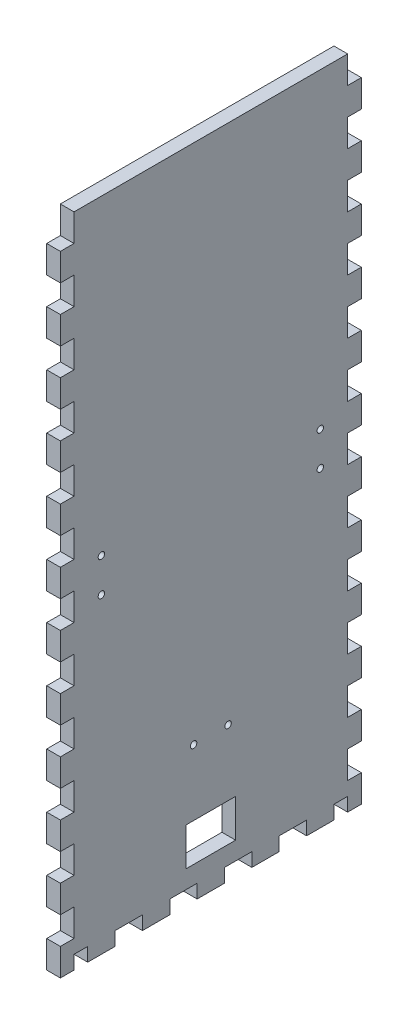
SolidWorks part; units mm, degrees
material "Acrylic (Medium-high impact)"
ref_plane "Front Plane" through (0, 0, 0) normal (0, 0, 1) x (1, 0, 0)
ref_plane "Top Plane" through (0, 0, 0) normal (0, 1, 0) x (1, 0, 0)
ref_plane "Right Plane" through (0, 0, 0) normal (1, 0, 0) x (0, 0, -1)
sketch "Sketch1" plane through (0, 0, 0) normal (0, 1, 0) x (1, 0, 0)
  line L1 (-136.525, 69.85) -> (136.525, 69.85)
  line L2 (-136.525, 69.85) -> (-136.525, -69.85)
  line L3 (-136.525, -69.85) -> (136.525, -69.85)
  line L4 (136.525, 69.85) -> (136.525, -69.85)
  point P4 (-136.525, 0)
  point P6 (0, 69.85)
  dimension "D1" = 139.7
  dimension "D2" = 273.05
extrude "Boss-Extrude1" add sketch "Sketch1" along normal blind 6.35
sketch "Sketch2" plane through (0, 6.35, 0) normal (0, 1, 0) x (1, 0, 0)
  line L0 (136.525, -69.85) -> (136.525, 69.85) construction
  line L1 (-136.525, 69.85) -> (136.525, 69.85)
  line L2 (-136.525, 69.85) -> (-136.525, -69.85)
  line L3 (-136.525, -69.85) -> (136.525, -69.85)
  line L4 (136.525, 69.85) -> (136.525, -69.85)
  line L5 (-136.525, -69.85) -> (136.525, -69.85) construction
  line L7 (-130.175, 63.5) -> (130.175, 63.5)
  line L8 (-130.175, 63.5) -> (-130.175, -63.5)
  line L9 (-130.175, -63.5) -> (130.175, -63.5)
  line L10 (130.175, 63.5) -> (130.175, -63.5)
  point P7 (-130.175, 0)
  point P14 (-136.525, 0)
  point P15 (0, -63.5)
  point P16 (0, -69.85)
  point P17 (130.175, 0)
  point P18 (136.525, 0)
  dimension "D1" = 6.35
  dimension "D2" = 6.35
extrude "Boss-Extrude2" add sketch "Sketch2" along normal blind 298.45
sketch "Sketch3" plane through (0, 0, 69.85) normal (0, 0, 1) x (1, 0, 0)
  line L0 (-25.273, 304.8) -> (-25.273, 0) construction
  line L2 (-130.175, 6.35) -> (130.175, 6.35) construction
  line L4 (-28.575, 283.21) -> (-28.575, 6.35)
  line L5 (-28.575, 6.35) -> (-21.971, 6.35)
  line L6 (-21.971, 292.354) -> (-21.971, 6.35)
  line L7 (-21.971, 292.354) -> (-41.529, 292.354)
  line L9 (-31.115, 285.75) -> (-41.529, 285.75)
  line L10 (-41.529, 292.354) -> (-41.529, 285.75)
  line L11 (-21.971, 101.6) -> (-9.271, 101.6) construction
  line L12 (-136.525, 0) -> (136.525, 0) construction
  line L13 (-12.446, 88.9) -> (-12.446, 101.6) construction
  line L14 (-15.621, 88.9) -> (-9.271, 88.9)
  line L15 (-15.621, 88.9) -> (-15.621, 71.9667)
  line L16 (-15.621, 71.9667) -> (-9.271, 71.9667)
  line L17 (-9.271, 88.9) -> (-9.271, 71.9667)
  line L18 (-15.621, 42.3333) -> (-9.271, 42.3333)
  line L19 (-15.621, 42.3333) -> (-15.621, 59.2667)
  line L20 (-15.621, 59.2667) -> (-9.271, 59.2667)
  line L21 (-9.271, 42.3333) -> (-9.271, 59.2667)
  line L26 (-15.621, 29.6333) -> (-9.271, 29.6333)
  line L27 (-15.621, 29.6333) -> (-15.621, 12.7)
  line L28 (-15.621, 12.7) -> (-9.271, 12.7)
  line L29 (-9.271, 29.6333) -> (-9.271, 12.7)
  line L30 (-12.446, 59.2667) -> (-12.446, 71.9667) construction
  line L31 (-12.446, 29.6333) -> (-12.446, 42.3333) construction
  line L32 (-12.446, 12.7) -> (-12.446, 0) construction
  line L33 (-136.525, 304.8) -> (136.525, 304.8) construction
  line L34 (-130.175, 304.8) -> (-130.175, 6.35) construction
  arc A0 (-28.575, 283.21) -> (-31.115, 285.75) centre (-31.115, 283.21) ccw
  point P5 (-25.273, 6.35)
  dimension "D5" = 2.54
  dimension "D1" = 6.604
  dimension "D2" = 12.954
  dimension "D3" = 6.604
  dimension "D4" = 286.004
  dimension "D6" = 101.6
  dimension "D7" = 12.7
  dimension "D8" = 12.7
  dimension "D9" = 6.35
  dimension "D10" = 101.6
extrude "Door Slot" cut sketch "Sketch3" against normal blind 12.7
sketch "Sketch4" plane through (0, 0, -63.5) normal (0, 0, 1) x (1, 0, 0)
  line L0 (-136.525, 304.8) -> (136.525, 304.8) construction
  line L1 (-47.879, 304.8) -> (-41.529, 304.8)
  line L2 (-47.879, 304.8) -> (-47.879, 6.35)
  line L3 (-47.879, 6.35) -> (-41.529, 6.35)
  line L4 (-41.529, 304.8) -> (-41.529, 6.35)
  line L5 (-18.796, 263.525) -> (-18.796, 247.65) construction
  line L6 (-41.529, 292.354) -> (-41.529, 285.75) construction
  line L7 (-21.971, 304.8) -> (-15.621, 304.8)
  line L8 (-21.971, 304.8) -> (-21.971, 6.35)
  line L9 (-21.971, 6.35) -> (-15.621, 6.35)
  line L10 (-15.621, 304.8) -> (-15.621, 6.35)
  line L11 (130.175, 6.35) -> (-130.175, 6.35) construction
  line L12 (-21.971, 6.35) -> (-21.971, 292.354) construction
  line L13 (-41.529, 304.8) -> (-47.879, 304.8)
  line L14 (-41.529, 304.8) -> (-41.529, 292.1)
  line L15 (-41.529, 292.1) -> (-47.879, 292.1)
  line L16 (-47.879, 304.8) -> (-47.879, 292.1)
  line L17 (-41.529, 276.225) -> (-47.879, 276.225)
  line L18 (-41.529, 276.225) -> (-41.529, 263.525)
  line L19 (-41.529, 263.525) -> (-47.879, 263.525)
  line L20 (-47.879, 276.225) -> (-47.879, 263.525)
  line L21 (-47.879, 6.35) -> (-41.529, 6.35)
  line L22 (-47.879, 6.35) -> (-47.879, 19.05)
  line L23 (-47.879, 19.05) -> (-41.529, 19.05)
  line L24 (-41.529, 6.35) -> (-41.529, 19.05)
  line L25 (-47.879, 34.925) -> (-41.529, 34.925)
  line L26 (-47.879, 34.925) -> (-47.879, 47.625)
  line L27 (-47.879, 47.625) -> (-41.529, 47.625)
  line L28 (-41.529, 34.925) -> (-41.529, 47.625)
  line L29 (-47.879, 92.075) -> (-41.529, 92.075)
  line L30 (-47.879, 92.075) -> (-47.879, 104.775)
  line L31 (-47.879, 104.775) -> (-41.529, 104.775)
  line L32 (-41.529, 92.075) -> (-41.529, 104.775)
  line L33 (-47.879, 149.225) -> (-41.529, 149.225)
  line L34 (-47.879, 149.225) -> (-47.879, 161.925)
  line L35 (-47.879, 161.925) -> (-41.529, 161.925)
  line L36 (-41.529, 149.225) -> (-41.529, 161.925)
  line L37 (-47.879, 177.8) -> (-41.529, 177.8)
  line L38 (-47.879, 177.8) -> (-47.879, 190.5)
  line L39 (-47.879, 190.5) -> (-41.529, 190.5)
  line L40 (-41.529, 177.8) -> (-41.529, 190.5)
  line L41 (-47.879, 206.375) -> (-41.529, 206.375)
  line L42 (-47.879, 206.375) -> (-47.879, 219.075)
  line L43 (-47.879, 219.075) -> (-41.529, 219.075)
  line L44 (-41.529, 206.375) -> (-41.529, 219.075)
  line L45 (-47.879, 234.95) -> (-41.529, 234.95)
  line L46 (-47.879, 234.95) -> (-47.879, 247.65)
  line L47 (-47.879, 247.65) -> (-41.529, 247.65)
  line L48 (-41.529, 234.95) -> (-41.529, 247.65)
  line L49 (-41.529, 133.35) -> (-47.879, 133.35)
  line L50 (-41.529, 133.35) -> (-41.529, 120.65)
  line L51 (-41.529, 120.65) -> (-47.879, 120.65)
  line L52 (-47.879, 133.35) -> (-47.879, 120.65)
  line L53 (-41.529, 76.2) -> (-47.879, 76.2)
  line L54 (-41.529, 76.2) -> (-41.529, 63.5)
  line L55 (-41.529, 63.5) -> (-47.879, 63.5)
  line L56 (-47.879, 76.2) -> (-47.879, 63.5)
  line L57 (-44.704, 304.8) -> (-44.704, 292.1) construction
  line L58 (-44.704, 292.1) -> (-44.704, 276.225) construction
  line L59 (-44.704, 276.225) -> (-44.704, 263.525) construction
  line L60 (-44.704, 247.65) -> (-44.704, 234.95) construction
  line L61 (-44.704, 234.95) -> (-44.704, 219.075) construction
  line L62 (-44.704, 219.075) -> (-44.704, 206.375) construction
  line L63 (-44.704, 206.375) -> (-44.704, 190.5) construction
  line L64 (-44.704, 190.5) -> (-44.704, 177.8) construction
  line L65 (-44.704, 177.8) -> (-44.704, 161.925) construction
  line L66 (-44.704, 161.925) -> (-44.704, 149.225) construction
  line L67 (-44.704, 133.35) -> (-44.704, 120.65) construction
  line L68 (-44.704, 120.65) -> (-44.704, 104.775) construction
  line L69 (-44.704, 104.775) -> (-44.704, 92.075) construction
  line L70 (-44.704, 92.075) -> (-44.704, 76.2) construction
  line L71 (-44.704, 76.2) -> (-44.704, 63.5) construction
  line L72 (-44.704, 63.5) -> (-44.704, 47.625) construction
  line L73 (-44.704, 47.625) -> (-44.704, 34.925) construction
  line L74 (-44.704, 34.925) -> (-44.704, 19.05) construction
  line L75 (-44.704, 19.05) -> (-44.704, 6.35) construction
  line L76 (-44.704, 149.225) -> (-44.704, 133.35) construction
  line L77 (-44.704, 263.525) -> (-44.704, 247.65) construction
  line L78 (-31.75, 304.8) -> (-31.75, 0) construction
  line L79 (136.525, 304.8) -> (-136.525, 304.8) construction
  line L80 (136.525, 0) -> (-136.525, 0) construction
  line L81 (-31.75, 8.3493) -> (-21.971, 8.3493) construction
  line L82 (-31.75, 8.3493) -> (-41.529, 8.3493) construction
  line L83 (-18.796, 149.225) -> (-18.796, 133.35) construction
  line L84 (-18.796, 19.05) -> (-18.796, 6.35) construction
  line L85 (-18.796, 34.925) -> (-18.796, 19.05) construction
  line L86 (-18.796, 47.625) -> (-18.796, 34.925) construction
  line L87 (-18.796, 63.5) -> (-18.796, 47.625) construction
  line L88 (-18.796, 76.2) -> (-18.796, 63.5) construction
  line L89 (-18.796, 92.075) -> (-18.796, 76.2) construction
  line L90 (-18.796, 104.775) -> (-18.796, 92.075) construction
  line L91 (-18.796, 120.65) -> (-18.796, 104.775) construction
  line L92 (-18.796, 133.35) -> (-18.796, 120.65) construction
  line L93 (-18.796, 161.925) -> (-18.796, 149.225) construction
  line L94 (-18.796, 177.8) -> (-18.796, 161.925) construction
  line L95 (-18.796, 190.5) -> (-18.796, 177.8) construction
  line L96 (-18.796, 206.375) -> (-18.796, 190.5) construction
  line L97 (-18.796, 219.075) -> (-18.796, 206.375) construction
  line L98 (-18.796, 234.95) -> (-18.796, 219.075) construction
  line L99 (-18.796, 247.65) -> (-18.796, 234.95) construction
  line L100 (-18.796, 276.225) -> (-18.796, 263.525) construction
  line L101 (-18.796, 292.1) -> (-18.796, 276.225) construction
  line L102 (-18.796, 304.8) -> (-18.796, 292.1) construction
  line L103 (-15.621, 76.2) -> (-15.621, 63.5)
  line L104 (-21.971, 63.5) -> (-15.621, 63.5)
  line L105 (-21.971, 76.2) -> (-21.971, 63.5)
  line L106 (-21.971, 76.2) -> (-15.621, 76.2)
  line L107 (-15.621, 133.35) -> (-15.621, 120.65)
  line L108 (-21.971, 120.65) -> (-15.621, 120.65)
  line L109 (-21.971, 133.35) -> (-21.971, 120.65)
  line L110 (-21.971, 133.35) -> (-15.621, 133.35)
  line L111 (-21.971, 234.95) -> (-21.971, 247.65)
  line L112 (-15.621, 247.65) -> (-21.971, 247.65)
  line L113 (-15.621, 234.95) -> (-15.621, 247.65)
  line L114 (-15.621, 234.95) -> (-21.971, 234.95)
  line L115 (-21.971, 206.375) -> (-21.971, 219.075)
  line L116 (-15.621, 219.075) -> (-21.971, 219.075)
  line L117 (-15.621, 206.375) -> (-15.621, 219.075)
  line L118 (-15.621, 206.375) -> (-21.971, 206.375)
  line L119 (-21.971, 177.8) -> (-21.971, 190.5)
  line L120 (-15.621, 190.5) -> (-21.971, 190.5)
  line L121 (-15.621, 177.8) -> (-15.621, 190.5)
  line L122 (-15.621, 177.8) -> (-21.971, 177.8)
  line L123 (-21.971, 149.225) -> (-21.971, 161.925)
  line L124 (-15.621, 161.925) -> (-21.971, 161.925)
  line L125 (-15.621, 149.225) -> (-15.621, 161.925)
  line L126 (-15.621, 149.225) -> (-21.971, 149.225)
  line L127 (-21.971, 92.075) -> (-21.971, 104.775)
  line L128 (-15.621, 104.775) -> (-21.971, 104.775)
  line L129 (-15.621, 92.075) -> (-15.621, 104.775)
  line L130 (-15.621, 92.075) -> (-21.971, 92.075)
  line L131 (-21.971, 34.925) -> (-21.971, 47.625)
  line L132 (-15.621, 47.625) -> (-21.971, 47.625)
  line L133 (-15.621, 34.925) -> (-15.621, 47.625)
  line L134 (-15.621, 34.925) -> (-21.971, 34.925)
  line L135 (-21.971, 6.35) -> (-21.971, 19.05)
  line L136 (-15.621, 19.05) -> (-21.971, 19.05)
  line L137 (-15.621, 6.35) -> (-15.621, 19.05)
  line L138 (-15.621, 6.35) -> (-21.971, 6.35)
  line L139 (-15.621, 276.225) -> (-15.621, 263.525)
  line L140 (-21.971, 263.525) -> (-15.621, 263.525)
  line L141 (-21.971, 276.225) -> (-21.971, 263.525)
  line L142 (-21.971, 276.225) -> (-15.621, 276.225)
  line L143 (-15.621, 304.8) -> (-15.621, 292.1)
  line L144 (-21.971, 292.1) -> (-15.621, 292.1)
  line L145 (-21.971, 304.8) -> (-21.971, 292.1)
  line L146 (-21.971, 304.8) -> (-15.621, 304.8)
  line L147 (-21.971, 304.8) -> (-21.971, 6.35)
  line L148 (-15.621, 6.35) -> (-21.971, 6.35)
  line L149 (-15.621, 304.8) -> (-15.621, 6.35)
  line L150 (-15.621, 304.8) -> (-21.971, 304.8)
  point P14 (-41.529, 289.052)
  dimension "D1" = 6.35
  dimension "D2" = 12.7
extrude "Door Guide Holes" cut sketch "Sketch4" against normal up to next contours L17 L4 L15 L2 | L2 L47 L4 L19 | L45 L2 L43 L4 | L41 L2 L39 L4 | L37 L2 L35 L4 | L49 L4 L33 L2 | L4 L51 L2 L31 | L53 L4 L29 L2 | L4 L55 L2 L27 | L25 L2 L23 L4 region at (-44.704, 284.1625, -63.5) region at (-44.704, 255.5875, -63.5) region at (-44.704, 227.0125, -63.5) region at (-44.704, 198.4375, -63.5) region at (-44.704, 169.8625, -63.5) region at (-44.704, 141.2875, -63.5) region at (-44.704, 112.7125, -63.5) region at (-44.704, 84.1375, -63.5) region at (-44.704, 55.5625, -63.5) region at (-44.704, 26.9875, -63.5)
ref_plane "Plane1" through (-31.75, 0, 0) normal (-1, 0, 0) x (0, 0, 1)
mirror "Mirror1" about plane through (-31.75, 0, 0) normal (-1, 0, 0) of "Door Guide Holes"
sketch "Lever Holes" plane through (0, 0, 69.85) normal (0, 0, 1) x (1, 0, 0)
  line L0 (49.276, 31.75) -> (58.928, 31.75)
  line L1 (49.276, 31.75) -> (49.276, 25.4)
  line L2 (49.276, 25.4) -> (58.928, 25.4)
  line L3 (58.928, 31.75) -> (58.928, 25.4)
  line L4 (36.1315, 19.05) -> (42.4815, 19.05)
  line L5 (36.1315, 19.05) -> (36.1315, 12.7)
  line L6 (36.1315, 12.7) -> (42.4815, 12.7)
  line L7 (42.4815, 19.05) -> (42.4815, 12.7)
  line L8 (65.7225, 19.05) -> (72.0725, 19.05)
  line L9 (65.7225, 19.05) -> (65.7225, 12.7)
  line L10 (65.7225, 12.7) -> (72.0725, 12.7)
  line L11 (72.0725, 19.05) -> (72.0725, 12.7)
  line L12 (42.4815, 15.875) -> (65.7225, 15.875) construction
  line L13 (-136.525, 0) -> (136.525, 0) construction
  line L14 (-21.971, 6.35) -> (130.175, 6.35) construction
  line L15 (130.175, 6.35) -> (-130.175, 6.35) construction
  point P12 (54.102, 15.875)
  point P13 (54.102, 25.4)
  point P24 (54.102, 6.35)
  dimension "D1" = 9.652
  dimension "D2" = 6.35
  dimension "D3" = 6.35
  dimension "D4" = 6.35
  dimension "D5" = 23.241
  dimension "D6" = 25.4
  dimension "D7" = 12.7
extrude "Cut-Extrude1" cut sketch "Lever Holes" against normal through all
sketch "Sketch8" plane through (-136.525, 0, 0) normal (-1, 0, 0) x (0, 0, 1)
  line L0 (-69.85, 0) -> (69.85, 0) construction
  circle A0 centre (0, 19.05) radius 3.175
  point P6 (0, 0)
  dimension "D1" = 6.35
  dimension "D2" = 19.05
extrude "Cut-Extrude3" cut sketch "Sketch8" against normal up to next
sketch "Bottom" plane through (0, 0, 0) normal (0, -1, 0) x (1, 0, 0)
  line L0 (-130.175, 63.5) -> (130.175, 63.5) construction
  line L1 (-136.525, 69.85) -> (-122.1539, 69.85)
  line L2 (-136.525, 69.85) -> (-136.525, 63.5)
  line L3 (-136.525, 63.5) -> (-122.1539, 63.5)
  line L4 (-122.1539, 69.85) -> (-122.1539, 63.5)
  line L5 (-122.1539, 69.85) -> (-107.7829, 69.85)
  line L6 (-122.1539, 69.85) -> (-122.1539, 63.5)
  line L7 (-122.1539, 63.5) -> (-107.7829, 63.5)
  line L8 (-107.7829, 69.85) -> (-107.7829, 63.5)
  line L9 (-107.7829, 69.85) -> (-93.4118, 69.85)
  line L10 (-107.7829, 69.85) -> (-107.7829, 63.5)
  line L11 (-107.7829, 63.5) -> (-93.4118, 63.5)
  line L12 (-93.4118, 69.85) -> (-93.4118, 63.5)
  line L13 (-93.4118, 69.85) -> (-79.0408, 69.85)
  line L14 (-93.4118, 69.85) -> (-93.4118, 63.5)
  line L15 (-93.4118, 63.5) -> (-79.0408, 63.5)
  line L16 (-79.0408, 69.85) -> (-79.0408, 63.5)
  line L17 (-136.525, 69.85) -> (136.525, 69.85) construction
  line L18 (-41.529, 63.5) -> (-21.971, 63.5) construction
  line L19 (-79.0408, 69.85) -> (-64.6697, 69.85)
  line L20 (-79.0408, 69.85) -> (-79.0408, 63.5)
  line L21 (-79.0408, 63.5) -> (-64.6697, 63.5)
  line L22 (-64.6697, 69.85) -> (-64.6697, 63.5)
  line L23 (-64.6697, 69.85) -> (-50.2987, 69.85)
  line L24 (-64.6697, 69.85) -> (-64.6697, 63.5)
  line L25 (-64.6697, 63.5) -> (-50.2987, 63.5)
  line L26 (-50.2987, 69.85) -> (-50.2987, 63.5)
  line L27 (-50.2987, 69.85) -> (-35.9276, 69.85)
  line L28 (-50.2987, 69.85) -> (-50.2987, 63.5)
  line L29 (-50.2987, 63.5) -> (-35.9276, 63.5)
  line L30 (-35.9276, 69.85) -> (-35.9276, 63.5)
  line L31 (-35.9276, 69.85) -> (-21.5566, 69.85)
  line L32 (-35.9276, 69.85) -> (-35.9276, 63.5)
  line L33 (-35.9276, 63.5) -> (-21.5566, 63.5)
  line L34 (-21.5566, 69.85) -> (-21.5566, 63.5)
  line L36 (-21.5566, 69.85) -> (-7.1855, 69.85)
  line L37 (-21.5566, 69.85) -> (-21.5566, 63.5)
  line L38 (-21.5566, 63.5) -> (-7.1855, 63.5)
  line L39 (-7.1855, 69.85) -> (-7.1855, 63.5)
  line L40 (-7.1855, 69.85) -> (7.1855, 69.85)
  line L41 (-7.1855, 69.85) -> (-7.1855, 63.5)
  line L42 (-7.1855, 63.5) -> (7.1855, 63.5)
  line L43 (7.1855, 69.85) -> (7.1855, 63.5)
  line L44 (7.1855, 69.85) -> (21.5566, 69.85)
  line L45 (7.1855, 69.85) -> (7.1855, 63.5)
  line L46 (7.1855, 63.5) -> (21.5566, 63.5)
  line L47 (21.5566, 69.85) -> (21.5566, 63.5)
  line L48 (21.5566, 69.85) -> (35.9276, 69.85)
  line L49 (21.5566, 69.85) -> (21.5566, 63.5)
  line L50 (21.5566, 63.5) -> (35.9276, 63.5)
  line L51 (35.9276, 69.85) -> (35.9276, 63.5)
  line L52 (35.9276, 69.85) -> (50.2987, 69.85)
  line L53 (35.9276, 69.85) -> (35.9276, 63.5)
  line L54 (35.9276, 63.5) -> (50.2987, 63.5)
  line L55 (50.2987, 69.85) -> (50.2987, 63.5)
  line L56 (50.2987, 69.85) -> (64.6697, 69.85)
  line L57 (50.2987, 69.85) -> (50.2987, 63.5)
  line L58 (50.2987, 63.5) -> (64.6697, 63.5)
  line L59 (64.6697, 69.85) -> (64.6697, 63.5)
  line L60 (64.6697, 69.85) -> (79.0408, 69.85)
  line L61 (64.6697, 69.85) -> (64.6697, 63.5)
  line L62 (64.6697, 63.5) -> (79.0408, 63.5)
  line L63 (79.0408, 69.85) -> (79.0408, 63.5)
  line L64 (79.0408, 69.85) -> (93.4118, 69.85)
  line L65 (79.0408, 69.85) -> (79.0408, 63.5)
  line L66 (79.0408, 63.5) -> (93.4118, 63.5)
  line L67 (93.4118, 69.85) -> (93.4118, 63.5)
  line L68 (93.4118, 69.85) -> (107.7829, 69.85)
  line L69 (93.4118, 69.85) -> (93.4118, 63.5)
  line L70 (93.4118, 63.5) -> (107.7829, 63.5)
  line L71 (107.7829, 69.85) -> (107.7829, 63.5)
  line L72 (107.7829, 69.85) -> (122.1539, 69.85)
  line L73 (107.7829, 69.85) -> (107.7829, 63.5)
  line L74 (107.7829, 63.5) -> (122.1539, 63.5)
  line L75 (122.1539, 69.85) -> (122.1539, 63.5)
  line L76 (-130.175, -63.5) -> (-130.175, 63.5) construction
  line L77 (-136.525, 69.85) -> (-130.175, 69.85)
  line L78 (-136.525, 69.85) -> (-136.525, 57.15)
  line L79 (-136.525, 57.15) -> (-130.175, 57.15)
  line L80 (-130.175, 69.85) -> (-130.175, 57.15)
  line L82 (-136.525, 57.15) -> (-130.175, 57.15)
  line L83 (-136.525, 57.15) -> (-136.525, 44.45)
  line L84 (-136.525, 44.45) -> (-130.175, 44.45)
  line L85 (-130.175, 57.15) -> (-130.175, 44.45)
  line L86 (-136.525, 44.45) -> (-130.175, 44.45)
  line L87 (-136.525, 44.45) -> (-136.525, 31.75)
  line L88 (-136.525, 31.75) -> (-130.175, 31.75)
  line L89 (-130.175, 44.45) -> (-130.175, 31.75)
  line L90 (-136.525, 31.75) -> (-130.175, 31.75)
  line L91 (-136.525, 31.75) -> (-136.525, 19.05)
  line L92 (-136.525, 19.05) -> (-130.175, 19.05)
  line L93 (-130.175, 31.75) -> (-130.175, 19.05)
  line L94 (-136.525, 19.05) -> (-130.175, 19.05)
  line L95 (-136.525, 19.05) -> (-136.525, 6.35)
  line L96 (-136.525, 6.35) -> (-130.175, 6.35)
  line L97 (-130.175, 19.05) -> (-130.175, 6.35)
  line L98 (-136.525, 6.35) -> (-130.175, 6.35)
  line L99 (-136.525, 6.35) -> (-136.525, -6.35)
  line L100 (-136.525, -6.35) -> (-130.175, -6.35)
  line L101 (-130.175, 6.35) -> (-130.175, -6.35)
  line L102 (-136.525, -6.35) -> (-130.175, -6.35)
  line L103 (-136.525, -6.35) -> (-136.525, -19.05)
  line L104 (-136.525, -19.05) -> (-130.175, -19.05)
  line L105 (-130.175, -6.35) -> (-130.175, -19.05)
  line L106 (-136.525, -19.05) -> (-130.175, -19.05)
  line L107 (-136.525, -19.05) -> (-136.525, -31.75)
  line L108 (-136.525, -31.75) -> (-130.175, -31.75)
  line L109 (-130.175, -19.05) -> (-130.175, -31.75)
  line L110 (-136.525, -31.75) -> (-130.175, -31.75)
  line L111 (-136.525, -31.75) -> (-136.525, -44.45)
  line L112 (-136.525, -44.45) -> (-130.175, -44.45)
  line L113 (-130.175, -31.75) -> (-130.175, -44.45)
  line L114 (-136.525, -44.45) -> (-130.175, -44.45)
  line L115 (-136.525, -44.45) -> (-136.525, -57.15)
  line L116 (-136.525, -57.15) -> (-130.175, -57.15)
  line L117 (-130.175, -44.45) -> (-130.175, -57.15)
  line L118 (136.525, 69.85) -> (136.525, -69.85) construction
  line L119 (122.1539, 69.85) -> (136.525, 69.85)
  line L120 (122.1539, 69.85) -> (122.1539, 63.5)
  line L121 (122.1539, 63.5) -> (136.525, 63.5)
  line L122 (136.525, 69.85) -> (136.525, 63.5)
  line L123 (136.525, -69.85) -> (-136.525, -69.85) construction
  line L124 (-136.525, -57.15) -> (-130.175, -57.15)
  line L125 (-136.525, -57.15) -> (-136.525, -69.85)
  line L126 (-136.525, -69.85) -> (-130.175, -69.85)
  line L127 (-130.175, -57.15) -> (-130.175, -69.85)
  line L128 (150.1775, 0) -> (-150.1775, 0) construction
  line L129 (136.525, -69.85) -> (136.525, -63.5)
  line L130 (122.1539, -63.5) -> (136.525, -63.5)
  line L131 (122.1539, -69.85) -> (136.525, -69.85)
  line L132 (122.1539, -69.85) -> (122.1539, -63.5)
  line L133 (107.7829, -63.5) -> (122.1539, -63.5)
  line L134 (107.7829, -69.85) -> (122.1539, -69.85)
  line L135 (107.7829, -69.85) -> (107.7829, -63.5)
  line L136 (93.4118, -63.5) -> (107.7829, -63.5)
  line L137 (93.4118, -69.85) -> (107.7829, -69.85)
  line L138 (93.4118, -69.85) -> (93.4118, -63.5)
  line L139 (79.0408, -63.5) -> (93.4118, -63.5)
  line L140 (79.0408, -69.85) -> (93.4118, -69.85)
  line L141 (79.0408, -69.85) -> (79.0408, -63.5)
  line L142 (64.6697, -63.5) -> (79.0408, -63.5)
  line L143 (64.6697, -69.85) -> (79.0408, -69.85)
  line L144 (50.2987, -63.5) -> (64.6697, -63.5)
  line L145 (64.6697, -69.85) -> (64.6697, -63.5)
  line L146 (50.2987, -69.85) -> (64.6697, -69.85)
  line L147 (50.2987, -69.85) -> (50.2987, -63.5)
  line L148 (35.9276, -63.5) -> (50.2987, -63.5)
  line L149 (35.9276, -69.85) -> (50.2987, -69.85)
  line L150 (35.9276, -69.85) -> (35.9276, -63.5)
  line L151 (21.5566, -63.5) -> (35.9276, -63.5)
  line L152 (21.5566, -69.85) -> (35.9276, -69.85)
  line L153 (21.5566, -69.85) -> (21.5566, -63.5)
  line L154 (7.1855, -69.85) -> (21.5566, -69.85)
  line L155 (7.1855, -63.5) -> (21.5566, -63.5)
  line L156 (7.1855, -69.85) -> (7.1855, -63.5)
  line L157 (-7.1855, -63.5) -> (7.1855, -63.5)
  line L158 (-7.1855, -69.85) -> (7.1855, -69.85)
  line L159 (-21.5566, -63.5) -> (-7.1855, -63.5)
  line L160 (-7.1855, -69.85) -> (-7.1855, -63.5)
  line L161 (-21.5566, -69.85) -> (-7.1855, -69.85)
  line L162 (-21.5566, -69.85) -> (-21.5566, -63.5)
  line L163 (-35.9276, -63.5) -> (-21.5566, -63.5)
  line L164 (-35.9276, -69.85) -> (-21.5566, -69.85)
  line L165 (-35.9276, -69.85) -> (-35.9276, -63.5)
  line L166 (-50.2987, -63.5) -> (-35.9276, -63.5)
  line L167 (-50.2987, -69.85) -> (-35.9276, -69.85)
  line L168 (-50.2987, -69.85) -> (-50.2987, -63.5)
  line L169 (-64.6697, -69.85) -> (-50.2987, -69.85)
  line L170 (-64.6697, -63.5) -> (-50.2987, -63.5)
  line L171 (-79.0408, -63.5) -> (-64.6697, -63.5)
  line L172 (-64.6697, -69.85) -> (-64.6697, -63.5)
  line L173 (-79.0408, -69.85) -> (-64.6697, -69.85)
  line L174 (-93.4118, -69.85) -> (-79.0408, -69.85)
  line L175 (-93.4118, -63.5) -> (-79.0408, -63.5)
  line L176 (-79.0408, -69.85) -> (-79.0408, -63.5)
  line L177 (-107.7829, -69.85) -> (-107.7829, -63.5)
  line L178 (-107.7829, -69.85) -> (-93.4118, -69.85)
  line L179 (-93.4118, -69.85) -> (-93.4118, -63.5)
  line L180 (-107.7829, -63.5) -> (-93.4118, -63.5)
  line L181 (-122.1539, -63.5) -> (-107.7829, -63.5)
  line L182 (-122.1539, -69.85) -> (-107.7829, -69.85)
  line L183 (-122.1539, -69.85) -> (-122.1539, -63.5)
  line L184 (-136.525, -69.85) -> (-122.1539, -69.85)
  line L185 (-136.525, -69.85) -> (-136.525, -63.5)
  line L186 (-136.525, -63.5) -> (-122.1539, -63.5)
  line L187 (0, -86.9215) -> (0, 86.9215) construction
  line L188 (136.525, -69.85) -> (130.175, -69.85)
  line L189 (130.175, -57.15) -> (130.175, -69.85)
  line L190 (136.525, -57.15) -> (136.525, -69.85)
  line L191 (136.525, -57.15) -> (130.175, -57.15)
  line L192 (130.175, -44.45) -> (130.175, -57.15)
  line L193 (136.525, -44.45) -> (136.525, -57.15)
  line L194 (136.525, -44.45) -> (130.175, -44.45)
  line L195 (130.175, -31.75) -> (130.175, -44.45)
  line L196 (136.525, -31.75) -> (136.525, -44.45)
  line L197 (136.525, -31.75) -> (130.175, -31.75)
  line L198 (136.525, -19.05) -> (136.525, -31.75)
  line L199 (130.175, -19.05) -> (130.175, -31.75)
  line L200 (130.175, -6.35) -> (130.175, -19.05)
  line L201 (136.525, -6.35) -> (136.525, -19.05)
  line L202 (136.525, -19.05) -> (130.175, -19.05)
  line L203 (136.525, -6.35) -> (130.175, -6.35)
  line L204 (130.175, 6.35) -> (130.175, -6.35)
  line L205 (136.525, 6.35) -> (136.525, -6.35)
  line L206 (136.525, 6.35) -> (130.175, 6.35)
  line L207 (130.175, 19.05) -> (130.175, 6.35)
  line L208 (136.525, 19.05) -> (136.525, 6.35)
  line L209 (136.525, 19.05) -> (130.175, 19.05)
  line L210 (136.525, 31.75) -> (130.175, 31.75)
  line L211 (136.525, 44.45) -> (130.175, 44.45)
  line L212 (136.525, 57.15) -> (130.175, 57.15)
  line L213 (130.175, 31.75) -> (130.175, 19.05)
  line L214 (136.525, 31.75) -> (136.525, 19.05)
  line L215 (130.175, 44.45) -> (130.175, 31.75)
  line L216 (136.525, 44.45) -> (136.525, 31.75)
  line L217 (130.175, 57.15) -> (130.175, 44.45)
  line L218 (136.525, 57.15) -> (136.525, 44.45)
  line L219 (130.175, 69.85) -> (130.175, 57.15)
  line L220 (136.525, 69.85) -> (136.525, 57.15)
sketch "Front/Back" plane through (0, 0, 69.85) normal (0, 0, 1) x (1, 0, 0)
  line L0 (-130.175, 6.35) -> (-28.575, 6.35) construction
  line L1 (-136.525, 0) -> (-122.1539, 0)
  line L2 (-136.525, 0) -> (-136.525, 6.35)
  line L3 (-136.525, 6.35) -> (-122.1539, 6.35)
  line L4 (-122.1539, 0) -> (-122.1539, 6.35)
  line L5 (-136.525, 0) -> (136.525, 0) construction
  line L6 (-107.7829, 0) -> (-93.4118, 0) construction
  line L7 (-122.1539, 6.35) -> (-107.7829, 6.35)
  line L8 (-122.1539, 6.35) -> (-122.1539, 0)
  line L9 (-122.1539, 0) -> (-107.7829, 0)
  line L10 (-107.7829, 6.35) -> (-107.7829, 0)
  line L11 (-79.0408, 0) -> (-64.6697, 0) construction
  line L12 (-107.7829, 6.35) -> (-93.4118, 6.35)
  line L13 (-107.7829, 6.35) -> (-107.7829, 0)
  line L14 (-107.7829, 0) -> (-93.4118, 0)
  line L15 (-93.4118, 6.35) -> (-93.4118, 0)
  line L16 (-93.4118, 6.35) -> (-79.0408, 6.35)
  line L17 (-93.4118, 6.35) -> (-93.4118, 0)
  line L18 (-93.4118, 0) -> (-79.0408, 0)
  line L19 (-79.0408, 6.35) -> (-79.0408, 0)
  line L20 (-64.6697, 0) -> (-50.2987, 0) construction
  line L21 (-79.0408, 6.35) -> (-64.6697, 6.35)
  line L22 (-79.0408, 6.35) -> (-79.0408, 0)
  line L23 (-79.0408, 0) -> (-64.6697, 0)
  line L24 (-64.6697, 6.35) -> (-64.6697, 0)
  line L25 (-64.6697, 6.35) -> (-50.2987, 6.35)
  line L26 (-64.6697, 6.35) -> (-64.6697, 0)
  line L27 (-64.6697, 0) -> (-50.2987, 0)
  line L28 (-50.2987, 6.35) -> (-50.2987, 0)
  line L29 (-50.2987, 0) -> (-35.9276, 0) construction
  line L30 (-50.2987, 6.35) -> (-35.9276, 6.35)
  line L31 (-50.2987, 6.35) -> (-50.2987, 0)
  line L32 (-50.2987, 0) -> (-35.9276, 0)
  line L33 (-35.9276, 6.35) -> (-35.9276, 0)
  line L34 (-21.5566, 0) -> (-7.1855, 0) construction
  line L35 (-35.9276, 6.35) -> (-21.5566, 6.35)
  line L36 (-35.9276, 6.35) -> (-35.9276, 0)
  line L37 (-35.9276, 0) -> (-21.5566, 0)
  line L38 (-21.5566, 6.35) -> (-21.5566, 0)
  line L39 (7.1855, 0) -> (21.5566, 0) construction
  line L40 (-21.5566, 6.35) -> (-7.1855, 6.35)
  line L41 (-21.5566, 6.35) -> (-21.5566, 0)
  line L42 (-21.5566, 0) -> (-7.1855, 0)
  line L43 (-7.1855, 6.35) -> (-7.1855, 0)
  line L44 (-7.1855, 6.35) -> (7.1855, 6.35)
  line L45 (-7.1855, 6.35) -> (-7.1855, 0)
  line L46 (-7.1855, 0) -> (7.1855, 0)
  line L47 (7.1855, 6.35) -> (7.1855, 0)
  line L48 (7.1855, 0) -> (21.5566, 0) construction
  line L49 (35.9276, 0) -> (50.2987, 0) construction
  line L50 (7.1855, 6.35) -> (21.5566, 6.35)
  line L51 (7.1855, 6.35) -> (7.1855, 0)
  line L52 (7.1855, 0) -> (21.5566, 0)
  line L53 (21.5566, 6.35) -> (21.5566, 0)
  line L54 (21.5566, 6.35) -> (35.9276, 6.35)
  line L55 (21.5566, 6.35) -> (21.5566, 0)
  line L56 (21.5566, 0) -> (35.9276, 0)
  line L57 (35.9276, 6.35) -> (35.9276, 0)
  line L58 (64.6697, 0) -> (79.0408, 0) construction
  line L59 (35.9276, 6.35) -> (50.2987, 6.35)
  line L60 (35.9276, 6.35) -> (35.9276, 0)
  line L61 (35.9276, 0) -> (50.2987, 0)
  line L62 (50.2987, 6.35) -> (50.2987, 0)
  line L63 (50.2987, 6.35) -> (64.6697, 6.35)
  line L64 (50.2987, 6.35) -> (50.2987, 0)
  line L65 (50.2987, 0) -> (64.6697, 0)
  line L66 (64.6697, 6.35) -> (64.6697, 0)
  line L67 (50.2987, 0) -> (64.6697, 0) construction
  line L68 (93.4118, 0) -> (107.7829, 0) construction
  line L69 (64.6697, 6.35) -> (79.0408, 6.35)
  line L70 (64.6697, 6.35) -> (64.6697, 0)
  line L71 (64.6697, 0) -> (79.0408, 0)
  line L72 (79.0408, 6.35) -> (79.0408, 0)
  line L73 (79.0408, 6.35) -> (93.4118, 6.35)
  line L74 (79.0408, 6.35) -> (79.0408, 0)
  line L75 (79.0408, 0) -> (93.4118, 0)
  line L76 (93.4118, 6.35) -> (93.4118, 0)
  line L77 (107.7829, 0) -> (122.1539, 0) construction
  line L78 (93.4118, 6.35) -> (107.7829, 6.35)
  line L79 (93.4118, 6.35) -> (93.4118, 0)
  line L80 (93.4118, 0) -> (107.7829, 0)
  line L81 (107.7829, 6.35) -> (107.7829, 0)
  line L82 (107.7829, 0) -> (122.1539, 0) construction
  line L84 (107.7829, 6.35) -> (122.1539, 6.35)
  line L85 (107.7829, 6.35) -> (107.7829, 0)
  line L86 (107.7829, 0) -> (122.1539, 0)
  line L87 (122.1539, 6.35) -> (122.1539, 0)
  line L88 (122.1539, 6.35) -> (136.525, 6.35)
  line L89 (122.1539, 6.35) -> (122.1539, 0)
  line L90 (122.1539, 0) -> (136.525, 0)
  line L91 (136.525, 6.35) -> (136.525, 0)
  line L92 (-130.175, 304.8) -> (-130.175, 6.35) construction
  line L93 (-136.525, 0) -> (-130.175, 0)
  line L94 (-136.525, 0) -> (-136.525, 12.7)
  line L95 (-136.525, 12.7) -> (-130.175, 12.7)
  line L96 (-130.175, 0) -> (-130.175, 12.7)
  line L97 (-136.525, 304.8) -> (-136.525, 0) construction
  line L98 (-136.525, 12.7) -> (-130.175, 12.7)
  line L99 (-136.525, 12.7) -> (-136.525, 25.4)
  line L100 (-136.525, 25.4) -> (-130.175, 25.4)
  line L101 (-130.175, 12.7) -> (-130.175, 25.4)
  line L102 (-136.525, 25.4) -> (-130.175, 25.4)
  line L103 (-136.525, 25.4) -> (-136.525, 38.1)
  line L104 (-136.525, 38.1) -> (-130.175, 38.1)
  line L105 (-130.175, 25.4) -> (-130.175, 38.1)
  line L106 (-136.525, 38.1) -> (-130.175, 38.1)
  line L107 (-136.525, 38.1) -> (-136.525, 50.8)
  line L108 (-136.525, 50.8) -> (-130.175, 50.8)
  line L109 (-130.175, 38.1) -> (-130.175, 50.8)
  line L110 (-136.525, 50.8) -> (-130.175, 50.8)
  line L111 (-136.525, 50.8) -> (-136.525, 63.5)
  line L112 (-136.525, 63.5) -> (-130.175, 63.5)
  line L113 (-130.175, 50.8) -> (-130.175, 63.5)
  line L114 (-136.525, 63.5) -> (-130.175, 63.5)
  line L115 (-136.525, 63.5) -> (-136.525, 76.2)
  line L116 (-136.525, 76.2) -> (-130.175, 76.2)
  line L117 (-130.175, 63.5) -> (-130.175, 76.2)
  line L118 (-136.525, 76.2) -> (-130.175, 76.2)
  line L119 (-136.525, 76.2) -> (-136.525, 88.9)
  line L120 (-136.525, 88.9) -> (-130.175, 88.9)
  line L121 (-130.175, 76.2) -> (-130.175, 88.9)
  line L122 (-136.525, 88.9) -> (-130.175, 88.9)
  line L123 (-136.525, 88.9) -> (-136.525, 101.6)
  line L124 (-136.525, 101.6) -> (-130.175, 101.6)
  line L125 (-130.175, 88.9) -> (-130.175, 101.6)
  line L126 (-136.525, 101.6) -> (-130.175, 101.6)
  line L127 (-136.525, 101.6) -> (-136.525, 114.3)
  line L128 (-136.525, 114.3) -> (-130.175, 114.3)
  line L129 (-130.175, 101.6) -> (-130.175, 114.3)
  line L130 (-136.525, 114.3) -> (-130.175, 114.3)
  line L131 (-136.525, 114.3) -> (-136.525, 127)
  line L132 (-136.525, 127) -> (-130.175, 127)
  line L133 (-130.175, 114.3) -> (-130.175, 127)
  line L134 (-136.525, 127) -> (-130.175, 127)
  line L135 (-136.525, 127) -> (-136.525, 139.7)
  line L136 (-136.525, 139.7) -> (-130.175, 139.7)
  line L137 (-130.175, 127) -> (-130.175, 139.7)
  line L138 (-136.525, 139.7) -> (-130.175, 139.7)
  line L139 (-136.525, 139.7) -> (-136.525, 152.4)
  line L140 (-136.525, 152.4) -> (-130.175, 152.4)
  line L141 (-130.175, 139.7) -> (-130.175, 152.4)
  line L142 (-136.525, 152.4) -> (-130.175, 152.4)
  line L143 (-136.525, 152.4) -> (-136.525, 165.1)
  line L144 (-136.525, 165.1) -> (-130.175, 165.1)
  line L145 (-130.175, 152.4) -> (-130.175, 165.1)
  line L146 (-136.525, 165.1) -> (-130.175, 165.1)
  line L147 (-136.525, 165.1) -> (-136.525, 177.8)
  line L148 (-136.525, 177.8) -> (-130.175, 177.8)
  line L149 (-130.175, 165.1) -> (-130.175, 177.8)
  line L150 (-136.525, 177.8) -> (-130.175, 177.8)
  line L151 (-136.525, 177.8) -> (-136.525, 190.5)
  line L152 (-136.525, 190.5) -> (-130.175, 190.5)
  line L153 (-130.175, 177.8) -> (-130.175, 190.5)
  line L154 (-136.525, 190.5) -> (-130.175, 190.5)
  line L155 (-136.525, 190.5) -> (-136.525, 203.2)
  line L156 (-136.525, 203.2) -> (-130.175, 203.2)
  line L157 (-130.175, 190.5) -> (-130.175, 203.2)
  line L158 (-136.525, 203.2) -> (-130.175, 203.2)
  line L159 (-136.525, 203.2) -> (-136.525, 215.9)
  line L160 (-136.525, 215.9) -> (-130.175, 215.9)
  line L161 (-130.175, 203.2) -> (-130.175, 215.9)
  line L162 (-136.525, 215.9) -> (-130.175, 215.9)
  line L163 (-136.525, 215.9) -> (-136.525, 228.6)
  line L164 (-136.525, 228.6) -> (-130.175, 228.6)
  line L165 (-130.175, 215.9) -> (-130.175, 228.6)
  line L166 (-136.525, 228.6) -> (-130.175, 228.6)
  line L167 (-136.525, 228.6) -> (-136.525, 241.3)
  line L168 (-136.525, 241.3) -> (-130.175, 241.3)
  line L169 (-130.175, 228.6) -> (-130.175, 241.3)
  line L170 (-136.525, 241.3) -> (-130.175, 241.3)
  line L171 (-136.525, 241.3) -> (-136.525, 254)
  line L172 (-136.525, 254) -> (-130.175, 254)
  line L173 (-130.175, 241.3) -> (-130.175, 254)
  line L174 (-136.525, 254) -> (-130.175, 254)
  line L175 (-136.525, 254) -> (-136.525, 266.7)
  line L176 (-136.525, 266.7) -> (-130.175, 266.7)
  line L177 (-130.175, 254) -> (-130.175, 266.7)
  line L178 (-136.525, 266.7) -> (-130.175, 266.7)
  line L179 (-136.525, 266.7) -> (-136.525, 279.4)
  line L180 (-136.525, 279.4) -> (-130.175, 279.4)
  line L181 (-130.175, 266.7) -> (-130.175, 279.4)
  line L182 (-136.525, 279.4) -> (-130.175, 279.4)
  line L183 (-136.525, 279.4) -> (-136.525, 292.1)
  line L184 (-136.525, 292.1) -> (-130.175, 292.1)
  line L185 (-130.175, 279.4) -> (-130.175, 292.1)
  line L186 (-136.525, 292.1) -> (-130.175, 292.1)
  line L187 (-136.525, 292.1) -> (-136.525, 304.8)
  line L188 (-136.525, 304.8) -> (-130.175, 304.8)
  line L189 (-130.175, 292.1) -> (-130.175, 304.8)
  line L190 (-136.525, 304.8) -> (-130.175, 304.8)
  line L194 (-136.525, 304.8) -> (136.525, 304.8) construction
  line L195 (0, -86.9215) -> (0, 86.9215) construction
  line L196 (136.525, 304.8) -> (130.175, 304.8)
  line L197 (130.175, 292.1) -> (130.175, 304.8)
  line L198 (136.525, 304.8) -> (130.175, 304.8)
  line L199 (136.525, 292.1) -> (136.525, 304.8)
  line L200 (136.525, 292.1) -> (130.175, 292.1)
  line L201 (130.175, 279.4) -> (130.175, 292.1)
  line L202 (136.525, 292.1) -> (130.175, 292.1)
  line L203 (136.525, 279.4) -> (136.525, 292.1)
  line L204 (136.525, 279.4) -> (130.175, 279.4)
  line L205 (130.175, 266.7) -> (130.175, 279.4)
  line L206 (136.525, 279.4) -> (130.175, 279.4)
  line L207 (136.525, 266.7) -> (136.525, 279.4)
  line L208 (136.525, 266.7) -> (130.175, 266.7)
  line L209 (130.175, 254) -> (130.175, 266.7)
  line L210 (136.525, 266.7) -> (130.175, 266.7)
  line L211 (136.525, 254) -> (136.525, 266.7)
  line L212 (136.525, 254) -> (130.175, 254)
  line L213 (130.175, 241.3) -> (130.175, 254)
  line L214 (136.525, 254) -> (130.175, 254)
  line L215 (136.525, 241.3) -> (136.525, 254)
  line L216 (136.525, 241.3) -> (130.175, 241.3)
  line L217 (130.175, 228.6) -> (130.175, 241.3)
  line L218 (136.525, 241.3) -> (130.175, 241.3)
  line L219 (136.525, 228.6) -> (136.525, 241.3)
  line L220 (136.525, 228.6) -> (130.175, 228.6)
  line L221 (130.175, 215.9) -> (130.175, 228.6)
  line L222 (136.525, 228.6) -> (130.175, 228.6)
  line L223 (136.525, 215.9) -> (136.525, 228.6)
  line L224 (136.525, 215.9) -> (130.175, 215.9)
  line L225 (130.175, 203.2) -> (130.175, 215.9)
  line L226 (136.525, 215.9) -> (130.175, 215.9)
  line L227 (136.525, 203.2) -> (136.525, 215.9)
  line L228 (136.525, 203.2) -> (130.175, 203.2)
  line L229 (130.175, 190.5) -> (130.175, 203.2)
  line L230 (136.525, 203.2) -> (130.175, 203.2)
  line L231 (136.525, 190.5) -> (136.525, 203.2)
  line L232 (136.525, 190.5) -> (130.175, 190.5)
  line L233 (130.175, 177.8) -> (130.175, 190.5)
  line L234 (136.525, 190.5) -> (130.175, 190.5)
  line L235 (136.525, 177.8) -> (136.525, 190.5)
  line L236 (136.525, 177.8) -> (130.175, 177.8)
  line L237 (130.175, 165.1) -> (130.175, 177.8)
  line L238 (136.525, 177.8) -> (130.175, 177.8)
  line L239 (136.525, 165.1) -> (136.525, 177.8)
  line L240 (136.525, 165.1) -> (130.175, 165.1)
  line L241 (130.175, 152.4) -> (130.175, 165.1)
  line L242 (136.525, 165.1) -> (130.175, 165.1)
  line L243 (136.525, 152.4) -> (136.525, 165.1)
  line L244 (136.525, 152.4) -> (130.175, 152.4)
  line L245 (130.175, 139.7) -> (130.175, 152.4)
  line L246 (136.525, 152.4) -> (130.175, 152.4)
  line L247 (136.525, 139.7) -> (136.525, 152.4)
  line L248 (136.525, 139.7) -> (130.175, 139.7)
  line L249 (130.175, 127) -> (130.175, 139.7)
  line L250 (136.525, 139.7) -> (130.175, 139.7)
  line L251 (136.525, 127) -> (136.525, 139.7)
  line L252 (136.525, 127) -> (130.175, 127)
  line L253 (130.175, 114.3) -> (130.175, 127)
  line L254 (136.525, 127) -> (130.175, 127)
  line L255 (136.525, 114.3) -> (136.525, 127)
  line L256 (136.525, 114.3) -> (130.175, 114.3)
  line L257 (130.175, 101.6) -> (130.175, 114.3)
  line L258 (136.525, 114.3) -> (130.175, 114.3)
  line L259 (136.525, 101.6) -> (136.525, 114.3)
  line L260 (136.525, 101.6) -> (130.175, 101.6)
  line L261 (130.175, 88.9) -> (130.175, 101.6)
  line L262 (136.525, 101.6) -> (130.175, 101.6)
  line L263 (136.525, 88.9) -> (136.525, 101.6)
  line L264 (136.525, 88.9) -> (130.175, 88.9)
  line L265 (130.175, 76.2) -> (130.175, 88.9)
  line L266 (136.525, 88.9) -> (130.175, 88.9)
  line L267 (136.525, 76.2) -> (136.525, 88.9)
  line L268 (136.525, 76.2) -> (130.175, 76.2)
  line L269 (130.175, 63.5) -> (130.175, 76.2)
  line L270 (136.525, 76.2) -> (130.175, 76.2)
  line L271 (136.525, 63.5) -> (136.525, 76.2)
  line L272 (136.525, 63.5) -> (130.175, 63.5)
  line L273 (130.175, 50.8) -> (130.175, 63.5)
  line L274 (136.525, 63.5) -> (130.175, 63.5)
  line L275 (136.525, 50.8) -> (136.525, 63.5)
  line L276 (136.525, 50.8) -> (130.175, 50.8)
  line L277 (130.175, 38.1) -> (130.175, 50.8)
  line L278 (136.525, 50.8) -> (130.175, 50.8)
  line L279 (136.525, 38.1) -> (136.525, 50.8)
  line L280 (136.525, 38.1) -> (130.175, 38.1)
  line L281 (130.175, 25.4) -> (130.175, 38.1)
  line L282 (136.525, 38.1) -> (130.175, 38.1)
  line L283 (136.525, 25.4) -> (136.525, 38.1)
  line L284 (136.525, 25.4) -> (130.175, 25.4)
  line L285 (130.175, 12.7) -> (130.175, 25.4)
  line L286 (136.525, 25.4) -> (130.175, 25.4)
  line L287 (136.525, 12.7) -> (136.525, 25.4)
  line L288 (136.525, 12.7) -> (130.175, 12.7)
  line L289 (130.175, 0) -> (130.175, 12.7)
  line L290 (136.525, 12.7) -> (130.175, 12.7)
  line L291 (136.525, 0) -> (136.525, 12.7)
  line L292 (136.525, 0) -> (130.175, 0)
  line L293 (136.525, 0) -> (136.525, 6.35)
sketch "Left/Right" plane through (-136.525, 0, 0) normal (-1, 0, 0) x (0, 0, 1)
  line L0 (57.15, 0) -> (44.45, 0) construction
  line L8 (57.15, 0) -> (57.15, 6.35)
  line L9 (57.15, 6.35) -> (44.45, 6.35)
  line L10 (57.15, 6.35) -> (57.15, 0)
  line L11 (57.15, 0) -> (44.45, 0)
  line L12 (44.45, 6.35) -> (44.45, 0)
  line L13 (-69.85, 0) -> (69.85, 0) construction
  line L14 (44.45, 0) -> (31.75, 0) construction
  line L15 (44.45, 6.35) -> (31.75, 6.35)
  line L16 (44.45, 6.35) -> (44.45, 0)
  line L17 (44.45, 0) -> (31.75, 0)
  line L18 (31.75, 6.35) -> (31.75, 0)
  line L19 (31.75, 0) -> (19.05, 0) construction
  line L20 (31.75, 6.35) -> (19.05, 6.35)
  line L21 (31.75, 6.35) -> (31.75, 0)
  line L22 (31.75, 0) -> (19.05, 0)
  line L23 (19.05, 6.35) -> (19.05, 0)
  line L24 (19.05, 0) -> (6.35, 0) construction
  line L25 (19.05, 6.35) -> (6.35, 6.35)
  line L26 (19.05, 6.35) -> (19.05, 0)
  line L27 (19.05, 0) -> (6.35, 0)
  line L28 (6.35, 6.35) -> (6.35, 0)
  line L29 (6.35, 0) -> (-6.35, 0) construction
  line L30 (6.35, 6.35) -> (-6.35, 6.35)
  line L31 (6.35, 6.35) -> (6.35, 0)
  line L32 (6.35, 0) -> (-6.35, 0)
  line L33 (-6.35, 6.35) -> (-6.35, 0)
  line L34 (-6.35, 0) -> (-19.05, 0) construction
  line L35 (-6.35, 6.35) -> (-19.05, 6.35)
  line L36 (-6.35, 6.35) -> (-6.35, 0)
  line L37 (-6.35, 0) -> (-19.05, 0)
  line L38 (-19.05, 6.35) -> (-19.05, 0)
  line L39 (-19.05, 0) -> (-31.75, 0) construction
  line L40 (-19.05, 6.35) -> (-31.75, 6.35)
  line L41 (-19.05, 6.35) -> (-19.05, 0)
  line L42 (-19.05, 0) -> (-31.75, 0)
  line L43 (-31.75, 6.35) -> (-31.75, 0)
  line L44 (-19.05, 0) -> (-31.75, 0) construction
  line L45 (-31.75, 0) -> (-44.45, 0) construction
  line L46 (-31.75, 6.35) -> (-44.45, 6.35)
  line L47 (-31.75, 6.35) -> (-31.75, 0)
  line L48 (-31.75, 0) -> (-44.45, 0)
  line L49 (-44.45, 6.35) -> (-44.45, 0)
  line L50 (69.85, 304.8) -> (69.85, 0) construction
  line L51 (-44.45, 6.35) -> (-57.15, 6.35)
  line L52 (-44.45, 6.35) -> (-44.45, 0)
  line L53 (-44.45, 0) -> (-57.15, 0)
  line L55 (-69.85, 0) -> (-63.5, 0) construction
  line L57 (-57.15, 6.35) -> (-57.15, 0)
  line L60 (-69.85, 0) -> (-63.5, 0) construction
  line L61 (69.85, 0) -> (57.15, 0) construction
  line L63 (-69.85, 6.35) -> (-69.85, 0)
  line L65 (57.15, 6.35) -> (69.85, 6.35)
  line L66 (57.15, 6.35) -> (57.15, 0)
  line L67 (57.15, 0) -> (69.85, 0)
  line L68 (69.85, 6.35) -> (69.85, 0)
  line L69 (69.85, 165.1) -> (69.85, 177.8) construction
  line L70 (63.5, 12.7) -> (69.85, 12.7)
  line L71 (63.5, 12.7) -> (63.5, 25.4)
  line L72 (63.5, 25.4) -> (69.85, 25.4)
  line L73 (-57.15, 0) -> (-69.85, 0)
  line L74 (-69.85, 6.35) -> (-57.15, 6.35)
  line L75 (-57.15, 0) -> (-69.85, 0) construction
  line L76 (69.85, 12.7) -> (69.85, 25.4)
  line L77 (69.85, 0) -> (63.5, 0)
  line L78 (69.85, 0) -> (69.85, 12.7)
  line L79 (69.85, 12.7) -> (63.5, 12.7)
  line L80 (63.5, 0) -> (63.5, 12.7)
  line L81 (63.5, 25.4) -> (69.85, 25.4)
  line L82 (63.5, 25.4) -> (63.5, 38.1)
  line L83 (63.5, 38.1) -> (69.85, 38.1)
  line L84 (69.85, 25.4) -> (69.85, 38.1)
  line L85 (63.5, 38.1) -> (69.85, 38.1)
  line L86 (63.5, 38.1) -> (63.5, 50.8)
  line L87 (63.5, 50.8) -> (69.85, 50.8)
  line L88 (69.85, 38.1) -> (69.85, 50.8)
  line L89 (63.5, 50.8) -> (69.85, 50.8)
  line L90 (63.5, 50.8) -> (63.5, 63.5)
  line L91 (63.5, 63.5) -> (69.85, 63.5)
  line L92 (69.85, 50.8) -> (69.85, 63.5)
  line L93 (63.5, 63.5) -> (69.85, 63.5)
  line L94 (63.5, 63.5) -> (63.5, 76.2)
  line L95 (63.5, 76.2) -> (69.85, 76.2)
  line L96 (69.85, 63.5) -> (69.85, 76.2)
  line L97 (63.5, 76.2) -> (69.85, 76.2)
  line L98 (63.5, 76.2) -> (63.5, 88.9)
  line L99 (63.5, 88.9) -> (69.85, 88.9)
  line L100 (69.85, 76.2) -> (69.85, 88.9)
  line L101 (63.5, 88.9) -> (69.85, 88.9)
  line L102 (63.5, 88.9) -> (63.5, 101.6)
  line L103 (63.5, 101.6) -> (69.85, 101.6)
  line L104 (69.85, 88.9) -> (69.85, 101.6)
  line L105 (63.5, 101.6) -> (69.85, 101.6)
  line L106 (63.5, 101.6) -> (63.5, 114.3)
  line L107 (63.5, 114.3) -> (69.85, 114.3)
  line L108 (69.85, 101.6) -> (69.85, 114.3)
  line L109 (63.5, 114.3) -> (69.85, 114.3)
  line L110 (63.5, 114.3) -> (63.5, 127)
  line L111 (63.5, 127) -> (69.85, 127)
  line L112 (69.85, 114.3) -> (69.85, 127)
  line L113 (63.5, 127) -> (69.85, 127)
  line L114 (63.5, 127) -> (63.5, 139.7)
  line L115 (63.5, 139.7) -> (69.85, 139.7)
  line L116 (69.85, 127) -> (69.85, 139.7)
  line L117 (63.5, 139.7) -> (69.85, 139.7)
  line L118 (63.5, 139.7) -> (63.5, 152.4)
  line L119 (63.5, 152.4) -> (69.85, 152.4)
  line L120 (69.85, 139.7) -> (69.85, 152.4)
  line L121 (63.5, 152.4) -> (69.85, 152.4)
  line L122 (63.5, 152.4) -> (63.5, 165.1)
  line L123 (63.5, 165.1) -> (69.85, 165.1)
  line L124 (69.85, 152.4) -> (69.85, 165.1)
  line L125 (63.5, 165.1) -> (69.85, 165.1)
  line L126 (63.5, 165.1) -> (63.5, 177.8)
  line L127 (63.5, 177.8) -> (69.85, 177.8)
  line L128 (69.85, 165.1) -> (69.85, 177.8)
  line L129 (63.5, 177.8) -> (69.85, 177.8)
  line L130 (63.5, 177.8) -> (63.5, 190.5)
  line L131 (63.5, 190.5) -> (69.85, 190.5)
  line L132 (69.85, 177.8) -> (69.85, 190.5)
  line L133 (69.85, 203.2) -> (69.85, 215.9) construction
  line L134 (63.5, 190.5) -> (69.85, 190.5)
  line L135 (63.5, 190.5) -> (63.5, 203.2)
  line L136 (63.5, 203.2) -> (69.85, 203.2)
  line L137 (69.85, 190.5) -> (69.85, 203.2)
  line L138 (63.5, 203.2) -> (69.85, 203.2)
  line L139 (63.5, 203.2) -> (63.5, 215.9)
  line L140 (63.5, 215.9) -> (69.85, 215.9)
  line L141 (69.85, 203.2) -> (69.85, 215.9)
  line L142 (63.5, 215.9) -> (69.85, 215.9)
  line L143 (63.5, 215.9) -> (63.5, 228.6)
  line L144 (63.5, 228.6) -> (69.85, 228.6)
  line L145 (69.85, 215.9) -> (69.85, 228.6)
  line L146 (69.85, 215.9) -> (69.85, 228.6) construction
  line L147 (63.5, 228.6) -> (69.85, 228.6)
  line L148 (63.5, 228.6) -> (63.5, 241.3)
  line L149 (63.5, 241.3) -> (69.85, 241.3)
  line L150 (69.85, 228.6) -> (69.85, 241.3)
  line L151 (0, -150.1775) -> (0, 150.1775) construction
  line L152 (63.5, 241.3) -> (69.85, 241.3)
  line L153 (63.5, 241.3) -> (63.5, 254)
  line L154 (63.5, 254) -> (69.85, 254)
  line L155 (69.85, 241.3) -> (69.85, 254)
  line L156 (63.5, 254) -> (69.85, 254)
  line L157 (63.5, 254) -> (63.5, 266.7)
  line L158 (63.5, 266.7) -> (69.85, 266.7)
  line L159 (69.85, 254) -> (69.85, 266.7)
  line L160 (63.5, 266.7) -> (69.85, 266.7)
  line L161 (63.5, 266.7) -> (63.5, 279.4)
  line L162 (63.5, 279.4) -> (69.85, 279.4)
  line L163 (69.85, 266.7) -> (69.85, 279.4)
  line L164 (63.5, 279.4) -> (69.85, 279.4)
  line L165 (63.5, 279.4) -> (63.5, 292.1)
  line L166 (63.5, 292.1) -> (69.85, 292.1)
  line L167 (69.85, 279.4) -> (69.85, 292.1)
  line L168 (63.5, 292.1) -> (69.85, 292.1)
  line L169 (63.5, 292.1) -> (63.5, 304.8)
  line L170 (63.5, 304.8) -> (69.85, 304.8)
  line L171 (69.85, 292.1) -> (69.85, 304.8)
  line L172 (-69.85, 292.1) -> (-69.85, 304.8)
  line L173 (-63.5, 304.8) -> (-69.85, 304.8)
  line L174 (-63.5, 292.1) -> (-63.5, 304.8)
  line L175 (-63.5, 292.1) -> (-69.85, 292.1)
  line L176 (-69.85, 279.4) -> (-69.85, 292.1)
  line L177 (-63.5, 292.1) -> (-69.85, 292.1)
  line L178 (-63.5, 279.4) -> (-63.5, 292.1)
  line L179 (-63.5, 279.4) -> (-69.85, 279.4)
  line L180 (-69.85, 266.7) -> (-69.85, 279.4)
  line L181 (-63.5, 279.4) -> (-69.85, 279.4)
  line L182 (-63.5, 266.7) -> (-63.5, 279.4)
  line L183 (-63.5, 266.7) -> (-69.85, 266.7)
  line L184 (-69.85, 254) -> (-69.85, 266.7)
  line L185 (-63.5, 266.7) -> (-69.85, 266.7)
  line L186 (-63.5, 254) -> (-63.5, 266.7)
  line L187 (-63.5, 254) -> (-69.85, 254)
  line L188 (-69.85, 241.3) -> (-69.85, 254)
  line L189 (-63.5, 254) -> (-69.85, 254)
  line L190 (-63.5, 241.3) -> (-63.5, 254)
  line L191 (-63.5, 241.3) -> (-69.85, 241.3)
  line L192 (-69.85, 228.6) -> (-69.85, 241.3)
  line L193 (-63.5, 241.3) -> (-69.85, 241.3)
  line L194 (-63.5, 228.6) -> (-63.5, 241.3)
  line L195 (-63.5, 228.6) -> (-69.85, 228.6)
  line L196 (-69.85, 215.9) -> (-69.85, 228.6)
  line L197 (-63.5, 228.6) -> (-69.85, 228.6)
  line L198 (-63.5, 215.9) -> (-63.5, 228.6)
  line L199 (-63.5, 215.9) -> (-69.85, 215.9)
  line L200 (-69.85, 203.2) -> (-69.85, 215.9)
  line L201 (-63.5, 215.9) -> (-69.85, 215.9)
  line L202 (-63.5, 203.2) -> (-63.5, 215.9)
  line L203 (-63.5, 203.2) -> (-69.85, 203.2)
  line L204 (-69.85, 190.5) -> (-69.85, 203.2)
  line L205 (-63.5, 203.2) -> (-69.85, 203.2)
  line L206 (-63.5, 190.5) -> (-63.5, 203.2)
  line L207 (-63.5, 190.5) -> (-69.85, 190.5)
  line L208 (-69.85, 177.8) -> (-69.85, 190.5)
  line L209 (-63.5, 190.5) -> (-69.85, 190.5)
  line L210 (-63.5, 177.8) -> (-63.5, 190.5)
  line L211 (-63.5, 177.8) -> (-69.85, 177.8)
  line L212 (-69.85, 165.1) -> (-69.85, 177.8)
  line L213 (-63.5, 177.8) -> (-69.85, 177.8)
  line L214 (-63.5, 165.1) -> (-63.5, 177.8)
  line L215 (-63.5, 165.1) -> (-69.85, 165.1)
  line L216 (-69.85, 152.4) -> (-69.85, 165.1)
  line L217 (-63.5, 165.1) -> (-69.85, 165.1)
  line L218 (-63.5, 152.4) -> (-63.5, 165.1)
  line L219 (-63.5, 152.4) -> (-69.85, 152.4)
  line L220 (-69.85, 139.7) -> (-69.85, 152.4)
  line L221 (-63.5, 152.4) -> (-69.85, 152.4)
  line L222 (-63.5, 139.7) -> (-63.5, 152.4)
  line L223 (-63.5, 139.7) -> (-69.85, 139.7)
  line L224 (-69.85, 127) -> (-69.85, 139.7)
  line L225 (-63.5, 139.7) -> (-69.85, 139.7)
  line L226 (-63.5, 127) -> (-63.5, 139.7)
  line L227 (-63.5, 127) -> (-69.85, 127)
  line L228 (-69.85, 114.3) -> (-69.85, 127)
  line L229 (-63.5, 127) -> (-69.85, 127)
  line L230 (-63.5, 114.3) -> (-63.5, 127)
  line L231 (-63.5, 114.3) -> (-69.85, 114.3)
  line L232 (-69.85, 101.6) -> (-69.85, 114.3)
  line L233 (-63.5, 114.3) -> (-69.85, 114.3)
  line L234 (-63.5, 101.6) -> (-63.5, 114.3)
  line L235 (-63.5, 101.6) -> (-69.85, 101.6)
  line L236 (-69.85, 88.9) -> (-69.85, 101.6)
  line L237 (-63.5, 101.6) -> (-69.85, 101.6)
  line L238 (-63.5, 88.9) -> (-63.5, 101.6)
  line L239 (-63.5, 88.9) -> (-69.85, 88.9)
  line L240 (-69.85, 76.2) -> (-69.85, 88.9)
  line L241 (-63.5, 88.9) -> (-69.85, 88.9)
  line L242 (-63.5, 76.2) -> (-63.5, 88.9)
  line L243 (-63.5, 76.2) -> (-69.85, 76.2)
  line L244 (-69.85, 63.5) -> (-69.85, 76.2)
  line L245 (-63.5, 76.2) -> (-69.85, 76.2)
  line L246 (-63.5, 63.5) -> (-63.5, 76.2)
  line L247 (-63.5, 63.5) -> (-69.85, 63.5)
  line L248 (-69.85, 50.8) -> (-69.85, 63.5)
  line L249 (-63.5, 63.5) -> (-69.85, 63.5)
  line L250 (-63.5, 50.8) -> (-63.5, 63.5)
  line L251 (-63.5, 50.8) -> (-69.85, 50.8)
  line L252 (-69.85, 38.1) -> (-69.85, 50.8)
  line L253 (-63.5, 50.8) -> (-69.85, 50.8)
  line L254 (-63.5, 38.1) -> (-63.5, 50.8)
  line L255 (-63.5, 38.1) -> (-69.85, 38.1)
  line L256 (-69.85, 25.4) -> (-69.85, 38.1)
  line L257 (-63.5, 38.1) -> (-69.85, 38.1)
  line L258 (-63.5, 25.4) -> (-63.5, 38.1)
  line L259 (-63.5, 25.4) -> (-69.85, 25.4)
  line L260 (-63.5, 0) -> (-63.5, 12.7)
  line L261 (-69.85, 12.7) -> (-63.5, 12.7)
  line L262 (-69.85, 0) -> (-69.85, 12.7)
  line L263 (-69.85, 0) -> (-63.5, 0)
  line L264 (-69.85, 12.7) -> (-69.85, 25.4)
  line L265 (-63.5, 25.4) -> (-69.85, 25.4)
  line L266 (-63.5, 12.7) -> (-63.5, 25.4)
  line L267 (-63.5, 12.7) -> (-69.85, 12.7)
  line L268 (-69.85, 6.35) -> (-69.85, 0)
  point P58 (63.5, 6.35)
  line M48 (-69.85, 0) -> (69.85, 0)
  line M49 (69.85, 0) -> (69.85, 304.8)
  line M50 (69.85, 304.8) -> (-69.85, 304.8)
  line M51 (-69.85, 304.8) -> (-69.85, 0)
sketch "Sketch15" plane through (-136.525, 0, 0) normal (-1, 0, 0) x (0, 0, 1)
  line L1 (-63.5, 304.8) -> (88.189, 304.8)
  line L2 (-63.5, 304.8) -> (-63.5, -23.6342)
  line L3 (-63.5, -23.6342) -> (88.189, -23.6342)
  line L4 (88.189, 304.8) -> (88.189, -23.6342)
sketch "Sketch16" plane through (0, 0, 69.85) normal (0, 0, 1) x (1, 0, 0)
  line L1 (-196.3018, 304.8) -> (130.175, 304.8)
  line L2 (-196.3018, 304.8) -> (-196.3018, -10.4336)
  line L3 (-196.3018, -10.4336) -> (130.175, -10.4336)
  line L4 (130.175, 304.8) -> (130.175, -10.4336)
extrude "Cut-Extrude10" cut sketch "Sketch16" against normal through all
extrude "Cut-Extrude11" cut sketch "Left/Right" against normal through all contours L72 L71 L70 M49 | L87 L86 L83 M49 | L95 L94 L91 M49 | L103 L102 L99 M49 | L111 L110 L107 M49 | L119 L118 L115 M49 | L127 L126 L123 M49 | L136 L135 L131 M49 | L144 L143 L140 M49 | L154 L153 L149 M49 | L162 L161 L158 M49 | L169 L166 M49 M50 | L175 L174 M50 M51 | L183 L182 L179 M51 | L191 L190 L187 M51 | L199 L198 L195 M51 | L207 L206 L203 M51 | L215 L214 L211 M51 | L223 L222 L219 M51 | L231 L230 L227 M51 | L239 L238 L235 M51 | L247 L246 L243 M51 | L255 L254 L251 M51 | L261 L266 L259 M51 | L15 L18 L12 M48 | L25 L28 L23 M48 | L35 L38 L33 M48 | L46 L49 L43 M48 | L260 L73 L57 L74 | L80 L65 L8 M48 region at (-136.525, 3.175, 60.325) region at (-136.525, 3.175, 38.1) region at (-136.525, 19.05, 66.675) region at (-136.525, 3.175, 12.7) region at (-136.525, 44.45, 66.675) region at (-136.525, 3.175, -12.7) region at (-136.525, 69.85, 66.675) region at (-136.525, 3.175, -38.1) region at (-136.525, 95.25, 66.675) region at (-136.525, 3.175, -60.325) region at (-136.525, 120.65, 66.675) region at (-136.525, 19.05, -66.675) region at (-136.525, 146.05, 66.675) region at (-136.525, 44.45, -66.675) region at (-136.525, 171.45, 66.675) region at (-136.525, 69.85, -66.675) region at (-136.525, 196.85, 66.675) region at (-136.525, 95.25, -66.675) region at (-136.525, 222.25, 66.675) region at (-136.525, 120.65, -66.675) region at (-136.525, 247.65, 66.675) region at (-136.525, 146.05, -66.675) region at (-136.525, 273.05, 66.675) region at (-136.525, 171.45, -66.675) region at (-136.525, 298.45, 66.675) region at (-136.525, 196.85, -66.675) region at (-136.525, 298.45, -66.675) region at (-136.525, 222.25, -66.675) region at (-136.525, 273.05, -66.675) region at (-136.525, 247.65, -66.675)
sketch "Sketch17" plane through (136.525, 0, 0) normal (1, 0, 0) x (0, 0, -1)
  line L0 (-8, 62.85) -> (8, 62.85) construction
  line L2 (-19.05, 6.35) -> (-6.35, 6.35) construction
  line L3 (6.35, 6.35) -> (19.05, 6.35) construction
  line L4 (-11.5, 32.35) -> (11.5, 32.35)
  line L5 (-11.5, 32.35) -> (-11.5, 14.732)
  line L6 (-11.5, 14.732) -> (11.5, 14.732)
  line L7 (11.5, 32.35) -> (11.5, 14.732)
  line L8 (-50.8, 160.275) -> (-50.8, 144.525) construction
  line L9 (-69.85, 292.1) -> (-69.85, 279.4) construction
  line L10 (-63.5, 304.8) -> (63.5, 304.8) construction
  line L11 (0, 304.8) -> (0, 0) construction
  line L12 (-6.35, 0) -> (6.35, 0) construction
  circle A0 centre (-8, 62.85) radius 1.5
  circle A1 centre (8, 62.85) radius 1.5
  circle A2 centre (-50.8, 160.275) radius 1.5
  circle A3 centre (-50.8, 144.525) radius 1.5
  circle A4 centre (50.8, 144.525) radius 1.5
  circle A5 centre (50.8, 160.275) radius 1.5
  point P4 (0, 62.85)
  point P12 (0, 14.732)
  point P31 (-50.8, 152.4)
  point P32 (0, 152.4)
  dimension "D1" = 3
  dimension "D8" = 3
  dimension "D2" = 16
  dimension "D3" = 56.5
  dimension "D4" = 8.382
  dimension "D5" = 26
  dimension "D6" = 23
  dimension "D7" = 15.75
  dimension "D9" = 19.05
extrude "Cut-Extrude12" cut sketch "Sketch17" against normal through all
